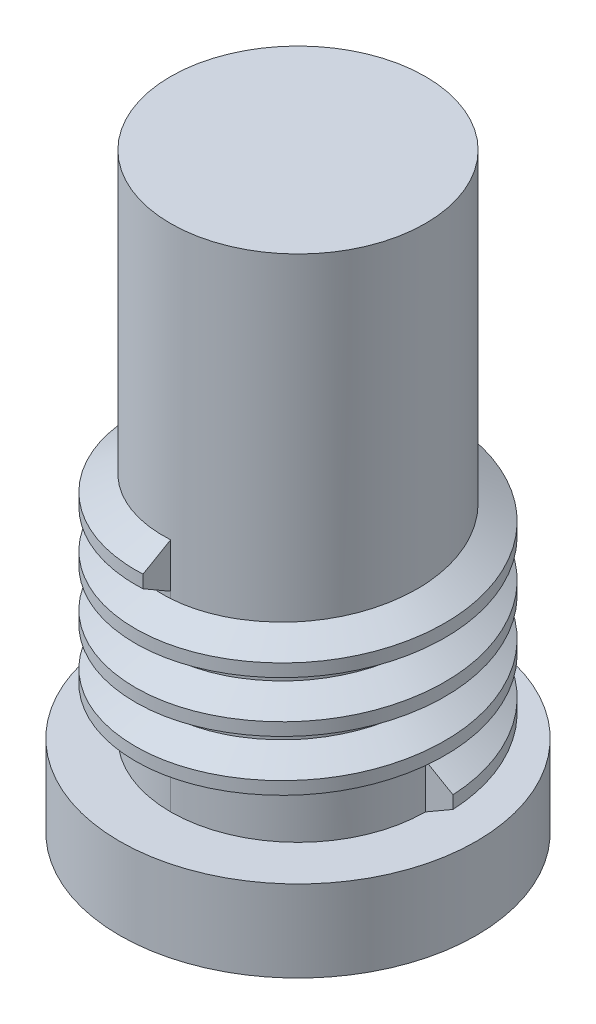
SolidWorks part; units mm, degrees
ref_plane "Front Plane" through (0, 0, 0) normal (0, 0, 1) x (1, 0, 0)
ref_plane "Top Plane" through (0, 0, 0) normal (0, 1, 0) x (1, 0, 0)
ref_plane "Right Plane" through (0, 0, 0) normal (1, 0, 0) x (0, 0, -1)
sketch "Sketch2" plane through (0, 0, 0) normal (0, 1, 0) x (1, 0, 0)
  circle A0 centre (0, 0) radius 3.175
  dimension "D1" = 6.35
extrude "Boss-Extrude1" add sketch "Sketch2" along normal blind 12.7
sketch "Sketch3" plane through (0, 0, 0) normal (0, -1, 0) x (-1, 0, 0)
  circle A0 centre (0, 0) radius 4.445
  dimension "D1" = 8.89
extrude "Boss-Extrude2" add sketch "Sketch3" along normal blind 2.032
thread "Thread1" pitch 1.27 method extrude profile "Thread Profile1" start angle 0, offset 0, length 4.7625, pitch 1.27, diameter 6.35
ref_plane "Plane1" through (3.175, 0, 0) normal (0, 0, -1) x (-1, 0, 0)
sketch "Thread Profile1" plane through (3.175, 0, 0) normal (0, 0, -1) x (-1, 0, 0)
  line L0 (0, 0) -> (0, 1.27) construction
  line L11 (0, 0) -> (0, 1.1112)
  line L12 (0, 1.1112) -> (-0.6874, 0.7144)
  line L13 (-0.6874, 0.7144) -> (-0.6874, 0.3969)
  line L15 (-0.6874, 0.3969) -> (0, 0)
  line L17 (-0.6874, 0.5556) -> (0, 0.5556) construction
  point P2 (0, 0)
  dimension "Pitch" = 1.27
  dimension "Profile_Angle" = 60
  dimension "Profile_Land" = 0.3175
  dimension "Profile_Height" = 0.6874
